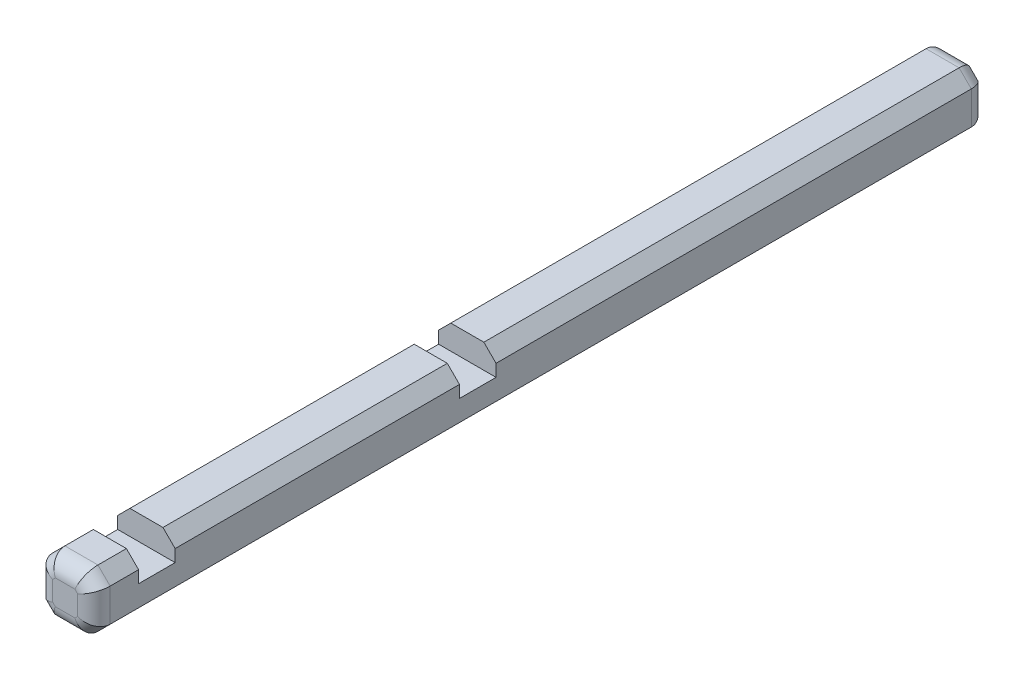
SolidWorks part; units mm, degrees
ref_plane "Front Plane" through (0, 0, 0) normal (0, 0, 1) x (1, 0, 0)
ref_plane "Top Plane" through (0, 0, 0) normal (0, 1, 0) x (1, 0, 0)
ref_plane "Right Plane" through (0, 0, 0) normal (1, 0, 0) x (0, 0, -1)
sketch "Sketch1" plane through (0, 0, 0) normal (0, 0, 1) x (1, 0, 0)
  line L1 (3.5355, -3.5355) -> (-3.5355, -3.5355)
  line L2 (3.5355, -3.5355) -> (3.5355, 3.5355)
  line L3 (3.5355, 3.5355) -> (-3.5355, 3.5355)
  line L4 (-3.5355, -3.5355) -> (-3.5355, 3.5355)
  point P0 (0, 3.5355)
  point P1 (-3.5355, 0)
  dimension "D1" = 7.0711
  dimension "D2" = 7.0711
extrude "Boss-Extrude1" add sketch "Sketch1" along normal blind 110
chamfer "Chamfer2" distance 1.5 angle 45 4 edges at (3.5355, -3.5355, 55) (-3.5355, -3.5355, 55) (3.5355, 3.5355, 55) (-3.5355, 3.5355, 55)
sketch "Sketch2" plane through (0, 0, 0) normal (0, 1, 0) x (1, 0, 0)
  line L0 (2.0355, -110) -> (-2.0355, -110) construction
  point P0 (0, -65)
  point P3 (0, -110)
  point P5 (0, -104.5)
  dimension "D1" = 45
  dimension "D2" = 5.5
ref_plane "Plane1" through (0, 0, 65) normal (0, 0, -1) x (-1, 0, 0)
sketch "Sketch3" plane through (0, 0, 65) normal (0, 0, -1) x (-1, 0, 0)
  line L0 (-3.5355, -2.0355) -> (-3.5355, 2.0355) construction
  line L1 (-3.5355, 0.5355) -> (3.5355, 0.5355)
  line L2 (-3.5355, 0.5355) -> (-3.5355, 3.5355)
  line L3 (-3.5355, 3.5355) -> (3.5355, 3.5355)
  line L4 (3.5355, 0.5355) -> (3.5355, 3.5355)
  line L5 (3.5355, 2.0355) -> (3.5355, -2.0355) construction
  line L6 (-2.0355, 3.5355) -> (2.0355, 3.5355) construction
  dimension "D1" = 3
extrude "Cut-Extrude1" cut sketch "Sketch3" along normal blind 4.5
ref_plane "Plane2" through (0, 0, 104.5) normal (0, 0, -1) x (-1, 0, 0)
sketch "Sketch4" plane through (0, 0, 104.5) normal (0, 0, -1) x (-1, 0, 0)
  line L0 (-3.5355, -2.0355) -> (-3.5355, 2.0355) construction
  line L1 (-3.5355, 0.5355) -> (3.5355, 0.5355)
  line L2 (-3.5355, 0.5355) -> (-3.5355, 3.5355)
  line L3 (-3.5355, 3.5355) -> (3.5355, 3.5355)
  line L4 (3.5355, 0.5355) -> (3.5355, 3.5355)
  line L5 (3.5355, 2.0355) -> (3.5355, -2.0355) construction
  line L6 (-2.0355, 3.5355) -> (2.0355, 3.5355) construction
  dimension "D1" = 3
extrude "Cut-Extrude2" cut sketch "Sketch4" along normal blind 4.5
fillet "Fillet1" radius 2 16 edges at (0, 3.5355, 0) (-3.5355, 0, 0) (0, -3.5355, 0) (3.5355, 0, 0) (-3.5355, 0, 110) (0, 3.5355, 110) (3.5355, 0, 110) (0, -3.5355, 110) (2.7855, 2.7855, 0) (-2.7855, 2.7855, 0) (-2.7855, -2.7855, 0) (2.7855, -2.7855, 0) (-2.7855, -2.7855, 110) (-2.7855, 2.7855, 110) (2.7855, 2.7855, 110) (2.7855, -2.7855, 110)
equation "\"thiccness\"=4.5"
equation "\"D1@Cut-Extrude1\"=\"thiccness\""
equation "\"cut\"=3"
equation "\"D1@Sketch4\"=\"cut\""
equation "\"D1@Cut-Extrude2\"=\"thiccness\""
equation "\"D1@Sketch3\"=\"cut\""
